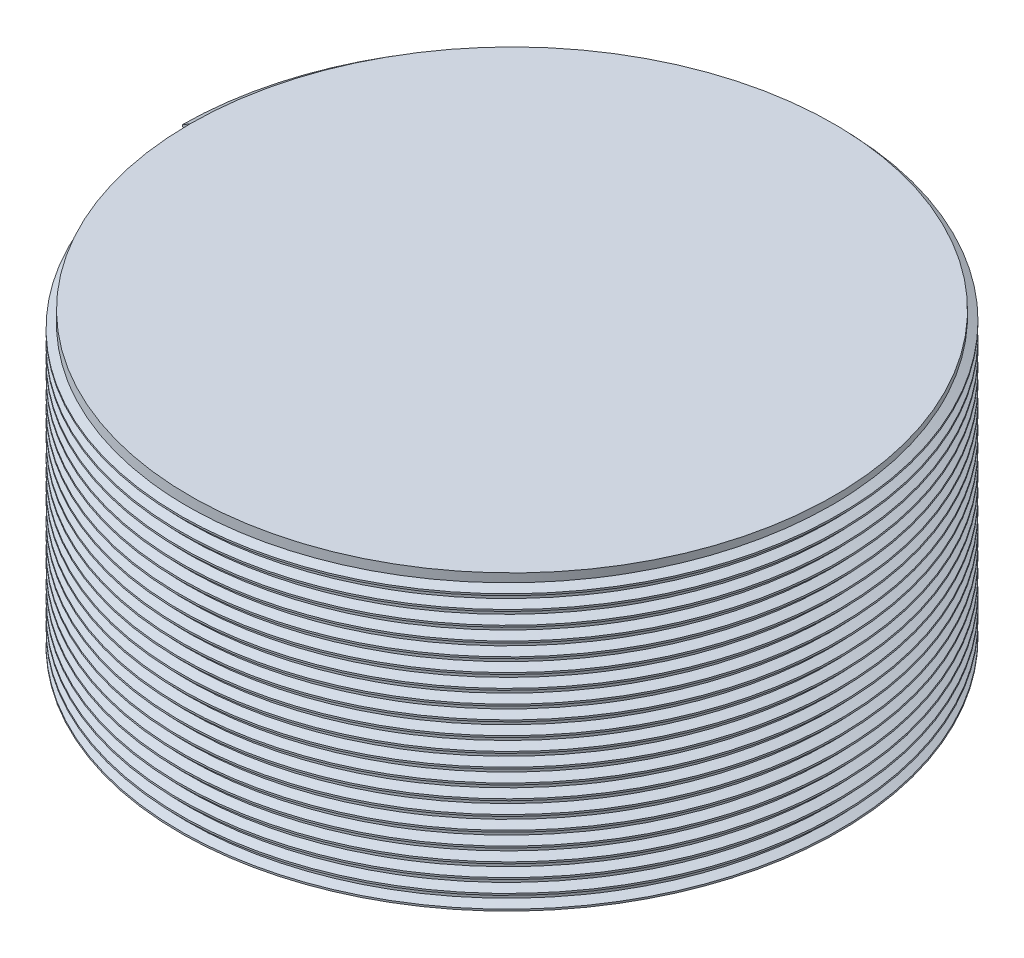
SolidWorks part; units mm, degrees
ref_plane "Front Plane" through (0, 0, 0) normal (0, 0, 1) x (1, 0, 0)
ref_plane "Top Plane" through (0, 0, 0) normal (0, 1, 0) x (1, 0, 0)
ref_plane "Right Plane" through (0, 0, 0) normal (1, 0, 0) x (0, 0, -1)
sketch "Sketch1" plane through (0, 0, 0) normal (0, 1, 0) x (1, 0, 0)
  circle A0 centre (0, 0) radius 14.15
  dimension "D1" = 28.3
extrude "Boss-Extrude1" add sketch "Sketch1" along normal blind 12.7
thread "MinColWidth_OnTracking1" pitch 0.6 method extrude profile "HeaderRowsCount1" start angle 0, offset 0, length 12.7, pitch 0.6, diameter 28.3
ref_plane "Plane1" through (-14.15, 12.7, 0) normal (0, 0, 1) x (-1, 0, 0)
sketch "HeaderRowsCount1" plane through (-14.15, 12.7, 0) normal (0, 0, 1) x (-1, 0, 0)
  line L0 (0, 0) -> (0, 0.6) construction
  line L1 (0, 0) -> (0.3248, 0.1875)
  line L2 (0.3248, 0.1875) -> (0.3248, 0.2625)
  line L3 (0.3248, 0.2625) -> (0, 0.45)
  line L4 (0.3248, 0.225) -> (0, 0.225) construction
  line L11 (0, 0) -> (0, 0.45)
  point P2 (0, 0)
  dimension "Pitch" = 0.6
  dimension "Profile_Angle" = 60
  dimension "Profile_Land" = 0.075
  dimension "Profile_Height" = 0.3248
